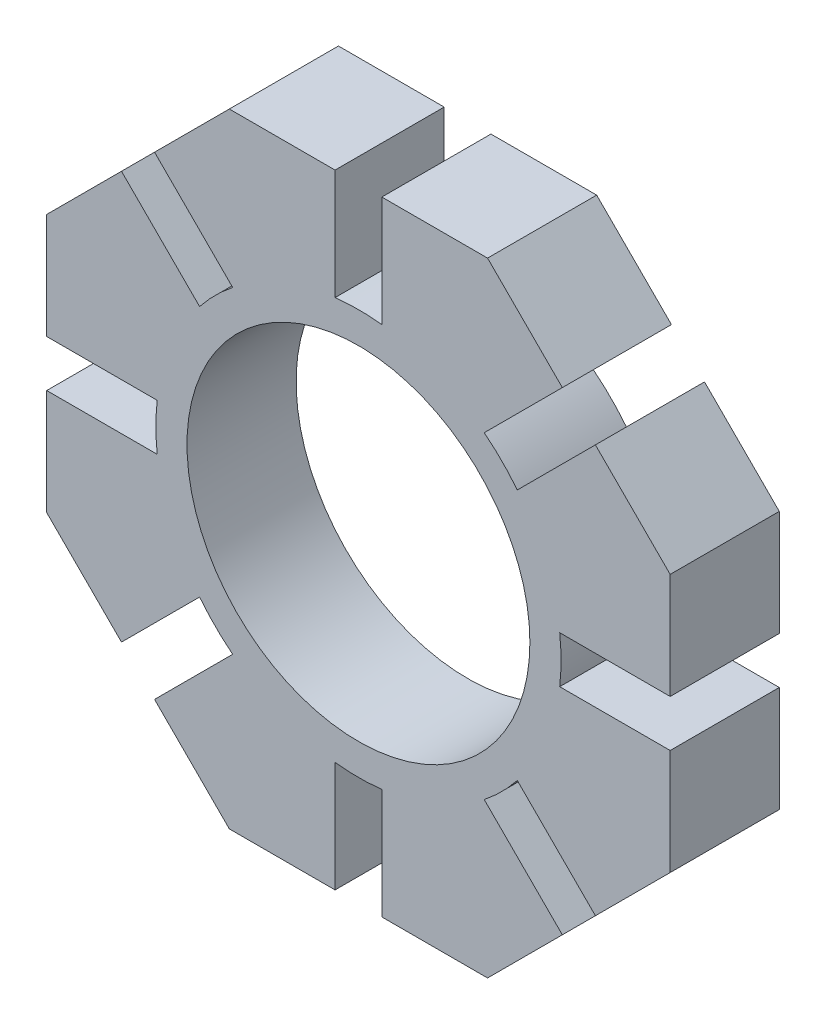
SolidWorks part; units mm, degrees
note: '?' marks a value the reader was unsure of.
ref_plane "Top Plane" through (0, 0, 0) normal (0, 0, 1) x (1, 0, 0)
ref_plane "Right Plane" through (0, 0, 0) normal (0, 1, 0) x (1, 0, 0)
ref_plane "Front Plane" through (0, 0, 0) normal (1, 0, 0) x (0, 0, -1)
ref_axis "x-axis" through (-88.99, 0, 0) along (1, 0, 0)?
ref_axis "y-axis" through (0, -55, 0) along (0, 1, 0)?
ref_axis "z-axis" through (0, 0, 55) along (0, 0, -1)?
sketch "Sketch1" plane through (0, 0, 0) normal (0, 0, 1) x (1, 0, 0)
  line L0 (8.2843, 20) -> (-8.2843, 20)
  line L1 (-20, 8.2843) -> (-20, -8.2843)
  line L2 (-20, -8.2843) -> (-8.2843, -20)
  line L3 (-8.2843, -20) -> (8.2843, -20)
  line L4 (8.2843, -20) -> (20, -8.2843)
  line L5 (20, -8.2843) -> (20, 8.2843)
  line L6 (20, 8.2843) -> (8.2843, 20)
  line L7 (-8.2843, 20) -> (-20, 8.2843)
  line L8 (-20, 0) -> (0, 0) construction
  circle A0 centre (0, 0) radius 11
  circle A1 centre (0, 0) radius 20 construction
  point P15 (11, 0)
  point P16 (-0.2636, -0.4614)
  point P17 (11, 0)
  dimension "D1" = 22
  dimension "D2" = 9
extrude "Boss-Extrude1" add sketch "Sketch1" along normal mid plane 7
sketch "Sketch2" plane through (0, -20, 0) normal (0, -1, 0) x (-1, 0, 0)
  line L0 (-8.2843, 3.5) -> (8.2843, -3.5) construction
  line L1 (-1.5, -4) -> (1.5, -4)
  line L2 (-1.5, -4) -> (-1.5, 4)
  line L3 (-1.5, 4) -> (1.5, 4)
  line L4 (1.5, -4) -> (1.5, 4)
  line L5 (-1.5, -4) -> (1.5, 4) construction
  line L6 (-1.5, 4) -> (1.5, -4) construction
  line L7 (-8.2843, -3.5) -> (8.2843, 3.5) construction
  point P13 (0, 0)
  point P14 (0, 0)
  point P15 (0, 0)
  dimension "D2" = 3
  dimension "D3" = 8
extrude "Cut-Extrude3" cut sketch "Sketch2" against normal offset from surface (7.0868 mm away) 2
pattern_circular "CirPattern1" count 8 over 360 about axis through (0, 0, 0) along (0, 0, 1) of "Cut-Extrude3"
